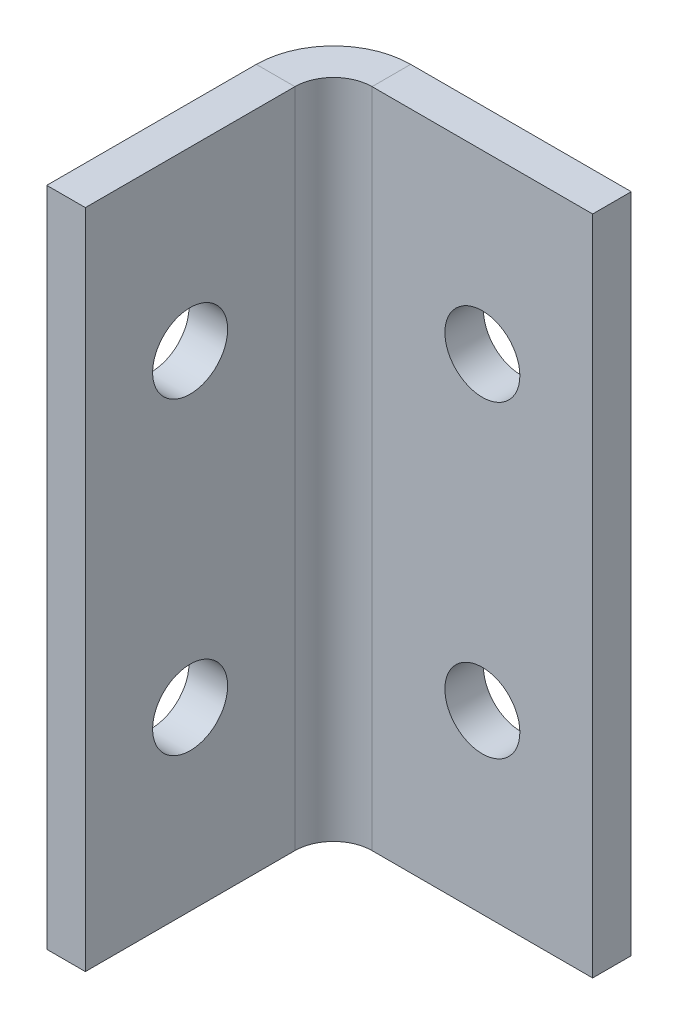
SolidWorks part; units mm, degrees
note: The reader was unsure of these and kept them because the rebuilt part matched: thickness of "Base-Flange1", "Edge-Flange1", "Sheet-Metal1", "Sheet-Metal2", "Sheet-Metal3"; flange length of "Edge-Flange1".
ref_plane "Front Plane" through (0, 0, 0) normal (0, 0, 1) x (1, 0, 0)
ref_plane "Top Plane" through (0, 0, 0) normal (0, 1, 0) x (1, 0, 0)
ref_plane "Right Plane" through (0, 0, 0) normal (1, 0, 0) x (0, 0, -1)
sketch "Sketch1" plane through (0, 0, 0) normal (0, 0, 1) x (1, 0, 0)
  line L1 (0, 0) -> (10, 0)
  line L2 (0, 0) -> (0, 30)
  line L3 (0, 30) -> (10, 30)
  line L4 (10, 0) -> (10, 30)
  dimension "D1" = 10
  dimension "D2" = 30
base flange "Base-Flange1" sketch "Sketch1" thickness 1.75 reverse thickness direction no parameters "D1"=1.75
edge flange "Edge-Flange1" sketch "Sketch8" flange angle 90 flange length 11.25 flange position bend outside bend radius 1.75 thickness 1.75 relief rectangular parameters "D6"=10
sketch "Sketch8" plane through (0, 0, 0) normal (-1, 0, 0) x (0, -1, 0)
  line L2 (-30, 0) -> (-30, 11.25)
  line L3 (-30, 11.25) -> (0, 11.25)
  line L4 (0, 11.25) -> (0, 0)
  line L7 (-30, 0) -> (0, 0) construction
  line L8 (-30, 0) -> (0, 0)
bend "EdgeBend1" bend radius 1.75 bend angle 90 parameters "D5"=1
sketch "Sketch9" plane through (0, 0, 0) normal (0, 0, 1) x (1, 0, 0)
  line L0 (5, 0) -> (5, 8) construction
  line L1 (0, 0) -> (10, 0) construction
  line L2 (5, 30) -> (5, 22) construction
  line L3 (10, 30) -> (0, 30) construction
  dimension "D1" = 8
sketch "Sketch10" plane through (-1.75, 0, 0) normal (1, 0, 0) x (0, 0, -1)
  line L0 (-6.5, 0) -> (-6.5, 8) construction
  line L1 (-1.75, 0) -> (-11.25, 0) construction
  line L2 (-6.5, 30) -> (-6.5, 22) construction
  line L3 (-11.25, 30) -> (-1.75, 30) construction
  dimension "D1" = 8
hole_wizard "M3 Clearance Hole1" positions "3DSketch1" profile "Sketch11" hole size "M3" standard "ANSI Metric"
sketch3d "3DSketch1"
  point P0 (5, 22, 0)
  point P3 (5, 8, 0)
  point P6 (-1.75, 22, 6.5)
  point P9 (-1.75, 8, 6.5)
sketch "Sketch11" plane through (5, 22, 0) normal (1, 0, 0) x (0, -1, 0)
  line L0 (0, 0) -> (0, 6.0215)
  line L1 (0, 6.0215) -> (1.7, 5)
  line L2 (1.7, 5) -> (1.7, 0)
  line L5 (1.7, 0) -> (0, 0)
  line L10 (0, 6.0215) -> (-1.7, 5) construction
  line L11 (0, -6.35) -> (0, 107.95) construction
  dimension "Hole Dia." = 3.4
  dimension "Hole Depth" = 5
  dimension "Drill Angle" = 118
sketch "Bend-Lines1" [suppressed] plane through (0, 0, 0) normal (0, 1, 0) x (1, 0, 0)
sketch "Bounding-Box1" [suppressed] plane through (0, 0, 0) normal (0, 1, 0) x (1, 0, 0)
sheet metal parameters "Sheet-Metal1" thickness 1.75 parameters "D1"=1.75, "D7"=1.016
flat pattern "Flat-Pattern1" [suppressed]
sketch "Bend-Lines2" plane through (0, 0, 0) normal (0, 1, 0) x (1, 0, 0)
sketch3d "Bounding-Box2" [suppressed]
  line L0 (10, 20, 0) -> (10, 0, 0) construction
  line L1 (0, 20, 0) -> (0, 0, 0) construction
  line L2 (10, 20, 0) -> (0, 20, 0) construction
  line L3 (10, 0, 0) -> (0, 0, 0) construction
sheet metal parameters "Sheet-Metal2" thickness 1.75 parameters "D1"=1.75, "D7"=1.016
flat pattern "Flat-Pattern1"
sketch "Bend-Lines2" plane through (0, 0, 0) normal (0, 0, 1) x (1, 0, 0)
  line L0 (-2.0617, 20) -> (-2.0617, 0) construction
  line L1 (-2.0617, 20) -> (-2.0617, 0) construction
sketch3d "Bounding-Box2" [suppressed]
  line L0 (-13.6233, 0, 0) -> (10, 0, 0) construction
  line L1 (-13.6233, 20, 0) -> (10, 20, 0) construction
  line L2 (-13.6233, 0, 0) -> (-13.6233, 20, 0) construction
  line L3 (10, 0, 0) -> (10, 20, 0) construction
bend of the flat pattern "Flatten-<EdgeBend1>1"
sheet metal parameters "Sheet-Metal3" thickness 1.75 parameters "D1"=1.75, "D7"=1.016
flat pattern "Flat-Pattern1" [suppressed]
sketch "Bend-Lines2" plane through (0, 0, 0) normal (0, 0, 1) x (1, 0, 0)
  line L0 (-2.0617, 30) -> (-2.0617, 0) construction
  line L1 (-2.0617, 30) -> (-2.0617, 0) construction
sketch3d "Bounding-Box2" [suppressed]
  line L0 (10, 30, 0) -> (10, 0, 0) construction
  line L1 (-13.6233, 30, 0) -> (-13.6233, 0, 0) construction
  line L2 (10, 30, 0) -> (-13.6233, 30, 0) construction
  line L3 (10, 0, 0) -> (-13.6233, 0, 0) construction
bend of the flat pattern "Flatten-<EdgeBend1>1"
sketch "Sketch10-1" [suppressed] plane through (-2.3733, 0, 0) normal (0, 0, 1) x (1, 0, 0)
  line L0 (-6.5, 0) -> (-6.5, 8) construction
  line L2 (-6.5, 30) -> (-6.5, 22) construction
  dimension "D1" = 8
